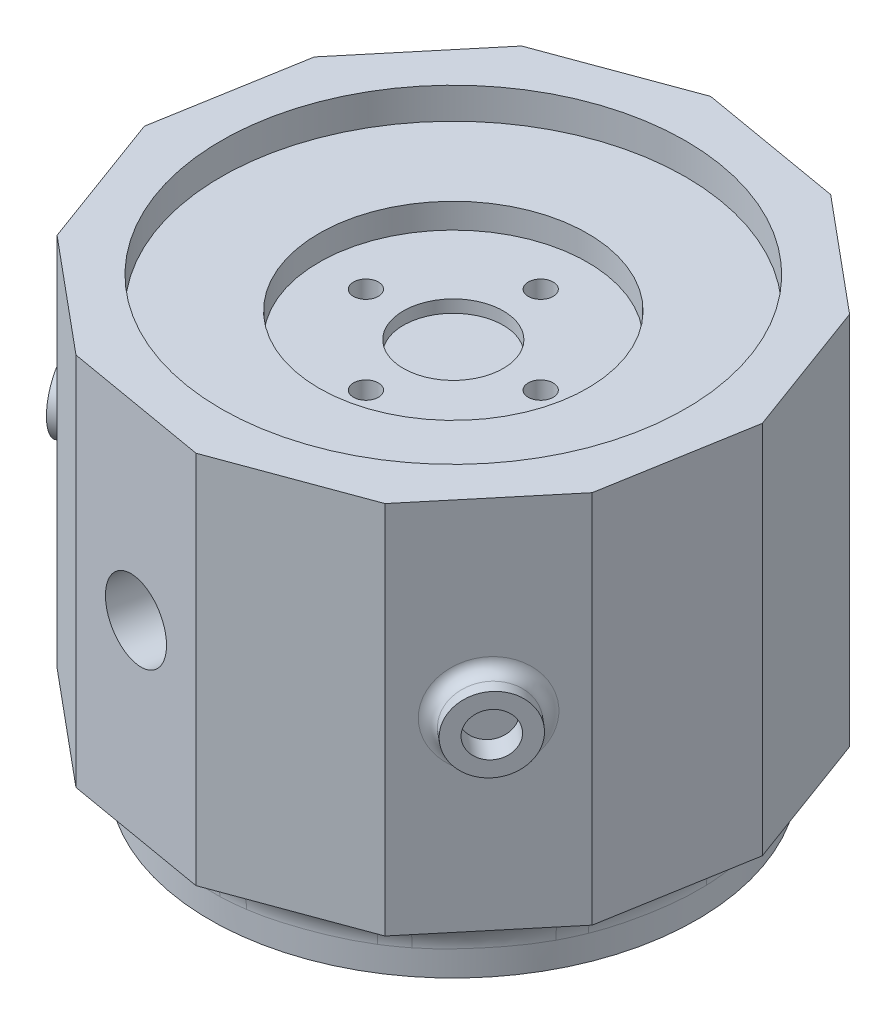
SolidWorks part; units mm, degrees
ref_plane "Front Plane" through (0, 0, 0) normal (0, 0, 1) x (1, 0, 0)
ref_plane "Top Plane" through (0, 0, 0) normal (0, 1, 0) x (1, 0, 0)
ref_plane "Right Plane" through (0, 0, 0) normal (1, 0, 0) x (0, 0, -1)
sketch "Sketch1" plane through (0, 0, 0) normal (0, 1, 0) x (1, 0, 0)
  line L0 (-18.6086, -13.1327) -> (-9.5492, -20.6776)
  line L1 (18.6086, 13.1327) -> (9.5492, 20.6776)
  line L2 (9.5492, 20.6776) -> (-2.0689, 22.6819)
  line L3 (-2.0689, 22.6819) -> (-13.1327, 18.6086)
  line L4 (-13.1327, 18.6086) -> (-20.6776, 9.5492)
  line L5 (-20.6776, 9.5492) -> (-22.6819, -2.0689)
  line L6 (-22.6819, -2.0689) -> (-18.6086, -13.1327)
  line L7 (-9.5492, -20.6776) -> (2.0689, -22.6819)
  line L8 (2.0689, -22.6819) -> (13.1327, -18.6086)
  line L9 (13.1327, -18.6086) -> (20.6776, -9.5492)
  line L10 (20.6776, -9.5492) -> (22.6819, 2.0689)
  line L11 (22.6819, 2.0689) -> (18.6086, 13.1327)
  circle A0 centre (0, 0) radius 22 construction
  circle A1 centre (0, 0) radius 18.6
  dimension "D1" = 37.2
  dimension "D2" = 44
extrude "Boss-Extrude1" add sketch "Sketch1" along normal blind 30
sketch "Sketch2" plane through (0, 30, 0) normal (0, 1, 0) x (1, 0, 0)
  circle A0 centre (0, 0) radius 18.6
  dimension "D1" = 37.2
extrude "Boss-Extrude2" add sketch "Sketch2" against normal blind 4.5 from offset 2.5 offset against normal yes
sketch "Sketch3" plane through (0, 23, 0) normal (0, -1, 0) x (1, 0, 0)
  circle A0 centre (0, 0) radius 15.5
  circle A1 centre (0, 0) radius 18.6
  dimension "D1" = 31
  dimension "D2" = 37.2
extrude "Cut-Extrude1" cut sketch "Sketch3" against normal blind 1.8
sketch "Sketch4" plane through (0, 0, 0) normal (0, -1, 0) x (1, 0, 0)
  circle A0 centre (0, 0) radius 18.6
  circle A1 centre (0, 0) radius 19.5
  dimension "D1" = 37.2
  dimension "D2" = 39
extrude "Boss-Extrude3" add sketch "Sketch4" along normal blind 5
fillet "Fillet1" radius 3 1 edges at (0, 0, 19.5)
sketch "Sketch5" plane through (3.7401, 0, -21.6797) normal (0.17, 0, -0.9854) x (-0.9854, 0, -0.17)
  line L0 (0, 30) -> (0, 0) construction
  line L1 (-5.8949, 30) -> (5.8949, 30) construction
  circle A0 centre (0, 15) radius 1.75
  circle A1 centre (0, 15) radius 3
  dimension "D2" = 3.5
  dimension "D3" = 6
  dimension "D1" = 15
extrude "Boss-Extrude4" add sketch "Sketch5" along normal blind 2
pattern_circular "CirPattern2" count 3 every 120 about axis through (0, -5, 0) along (0, -1, 0) of "Boss-Extrude4"
fillet "Fillet2" radius 1 3 edges at (6.6965, 15, -21.1697) (-21.6818, 15, 4.7856) (14.9853, 15, 16.3842)
sketch "Sketch6" plane through (0, 27.5, 0) normal (0, 1, 0) x (1, 0, 0)
  line L0 (0, 0) -> (18.6, 0) construction
  circle A0 centre (0, 0) radius 4
  circle A1 centre (0, 0) radius 18.6 construction
  circle A2 centre (7, 0) radius 1
  circle A3 centre (0, 0) radius 10.75
  circle A4 centre (0, -7) radius 1
  circle A5 centre (-7, 0) radius 1
  circle A6 centre (0, 7) radius 1
  point P19 (0, 0)
  dimension "D1" = 8
  dimension "D3" = 2
  dimension "D4" = 21.5
  dimension "D2" = 7
  dimension "D5" = 4
extrude "Cut-Extrude5" cut sketch "Sketch6" against normal blind 2 contours A0 A2 A3 A6 A5 A4 | A0 region at (0, 27.5, 0) region at (-10.4459, 27.5, 0)
extrude "Cut-Extrude6" cut sketch "Sketch6<3>" against normal blind 1 from surface contours A0 region at (0, 27.5, 0) starting at face at (7, 25.5, 1)
sketch "Sketch6<3>" plane through (0, 27.5, 0) normal (0, 1, 0) x (1, 0, 0) same geometry as "Sketch6"
extrude "Cut-Extrude7" cut sketch "Sketch6<4>" against normal through all both and the other way through all contours A5 | A6 | A4 | L0 A2 | A2 L0 region at (7, 27.5, 0.4244) region at (7, 27.5, -0.4244) region at (0, 27.5, 7) region at (-7, 27.5, 0) region at (0, 27.5, -7)
sketch "Sketch6<4>" plane through (0, 27.5, 0) normal (0, 1, 0) x (1, 0, 0) same geometry as "Sketch6"
sketch "Sketch7" plane through (-3.7401, 0, 21.6797) normal (-0.17, 0, 0.9854) x (0.9854, 0, 0.17)
  line L0 (0, 0) -> (0, 30) construction
  line L1 (-5.8949, 30) -> (5.8949, 30) construction
  line L2 (-4.717, 0) -> (4.717, 0) construction
  circle A0 centre (0, 15) radius 3
  dimension "D2" = 6
  dimension "D1" = 15
extrude "Cut-Extrude8" cut sketch "Sketch7" against normal blind 10
